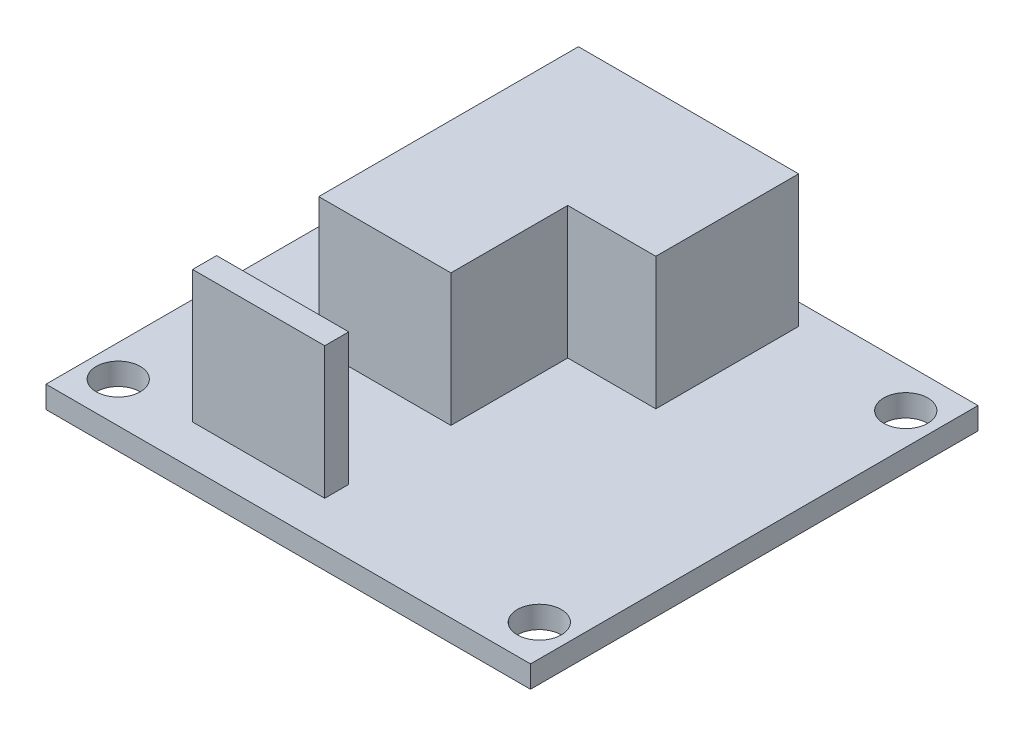
SolidWorks part; units mm, degrees
ref_plane "Front" through (0, 0, 0) normal (0, 0, 1) x (1, 0, 0)
ref_plane "Top" through (0, 0, 0) normal (0, 1, 0) x (1, 0, 0)
ref_plane "Right" through (0, 0, 0) normal (1, 0, 0) x (0, 0, -1)
sketch "Sketch2" plane through (0, 0, 0) normal (0, 1, 0) x (1, 0, 0)
  line L0 (0, -55) -> (0, 55) construction
  line L1 (-17.4625, 16.129) -> (17.4625, 16.129)
  line L2 (-17.4625, 16.129) -> (-17.4625, -16.129)
  line L3 (-17.4625, -16.129) -> (17.4625, -16.129)
  line L4 (17.4625, 16.129) -> (17.4625, -16.129)
  line L5 (-17.4625, 16.129) -> (17.4625, -16.129) construction
  line L6 (-17.4625, -16.129) -> (17.4625, 16.129) construction
  line L7 (-55, 0) -> (55, 0) construction
  line L9 (-9.8168, 14.6038) -> (-0.2918, 14.6038)
  line L10 (-9.8168, 14.6038) -> (-9.8168, -4.1127)
  line L11 (-9.8168, -4.1127) -> (-0.2918, -4.1127)
  line L12 (-0.2918, 14.6038) -> (-0.2918, -4.1127)
  line L13 (-0.2918, 14.6038) -> (6.0582, 14.6038)
  line L14 (-0.2918, 14.6038) -> (-0.2918, 4.3097)
  line L15 (-0.2918, 4.3097) -> (6.0582, 4.3097)
  line L16 (6.0582, 14.6038) -> (6.0582, 4.3097)
  line L17 (-9.8168, -11.4774) -> (-0.2918, -11.4774)
  line L18 (-9.8168, -11.4774) -> (-9.8168, -13.208)
  line L19 (-9.8168, -13.208) -> (-0.2918, -13.208)
  line L20 (-0.2918, -11.4774) -> (-0.2918, -13.208)
  circle A0 centre (-15.1765, 13.208) radius 1.5875
  circle A1 centre (15.1765, 13.208) radius 1.5875
  circle A2 centre (15.1765, -13.208) radius 1.5875
  circle A3 centre (-15.1765, -13.208) radius 1.5875
  point P0 (0, 0)
  dimension "D3" = 3.175
  dimension "D1" = 34.925
  dimension "D2" = 32.258
  dimension "D4" = 2.921
  dimension "D5" = 2.286
  dimension "D6" = 15.875
  dimension "D7" = 9.525
  dimension "D8" = 6.35
extrude "Boss-Extrude1" add sketch "Sketch2" along normal blind 1.5875 contours L4 L1 L2 L3 A1 A0 L13 L16 L15 L12 L11 L10 L9 L17 L20 L19 L18 A2 A3 region at (0.9534, 0, 1.617)
sketch "Sketch3" plane through (0, 1.5875, 0) normal (0, 1, 0) x (1, 0, 0)
  line L0 (-9.8168, 14.6038) -> (6.0582, 14.6038) construction
  line L1 (-9.8168, 14.6038) -> (-9.8168, -4.1127) construction
  line L2 (-9.8168, -4.1127) -> (-0.2918, -4.1127) construction
  line L3 (-0.2918, 4.3097) -> (-0.2918, -4.1127) construction
  line L4 (17.4625, -16.129) -> (17.4625, 16.129)
  line L5 (17.4625, 16.129) -> (-17.4625, 16.129)
  line L6 (-17.4625, 16.129) -> (-17.4625, -16.129)
  line L7 (-17.4625, -16.129) -> (17.4625, -16.129)
  line L8 (17.4625, -16.129) -> (17.4625, 16.129)
  line L9 (17.4625, 16.129) -> (-17.4625, 16.129)
  line L10 (-17.4625, 16.129) -> (-17.4625, -16.129)
  line L11 (-17.4625, -16.129) -> (17.4625, -16.129)
  line L12 (-0.2918, 4.3097) -> (6.0582, 4.3097) construction
  line L13 (6.0582, 14.6038) -> (6.0582, 4.3097) construction
  line L14 (-0.2918, -11.4774) -> (-0.2918, -13.208) construction
  line L15 (-9.8168, -11.4774) -> (-0.2918, -11.4774) construction
  line L16 (-9.8168, -11.4774) -> (-9.8168, -13.208) construction
  line L17 (-9.8168, -13.208) -> (-0.2918, -13.208) construction
  line L18 (-9.8168, -13.208) -> (-0.2918, -13.208)
  line L19 (-9.8168, -11.4774) -> (-9.8168, -13.208)
  line L20 (-9.8168, -11.4774) -> (-0.2918, -11.4774)
  line L21 (-0.2918, -11.4774) -> (-0.2918, -13.208)
  line L22 (6.0582, 14.6038) -> (6.0582, 4.3097)
  line L23 (-0.2918, 4.3097) -> (6.0582, 4.3097)
  line L24 (-0.2918, 4.3097) -> (-0.2918, -4.1127)
  line L25 (-9.8168, -4.1127) -> (-0.2918, -4.1127)
  line L26 (-9.8168, 14.6038) -> (-9.8168, -4.1127)
  line L27 (-9.8168, 14.6038) -> (6.0582, 14.6038)
  line M21 (-9.8168, 14.6038) -> (6.0582, 14.6038)
  line M22 (6.0582, 14.6038) -> (6.0582, 4.3097)
  line M23 (6.0582, 4.3097) -> (-0.2918, 4.3097)
  line M24 (-0.2918, 4.3097) -> (-0.2918, -4.1127)
  line M25 (-0.2918, -4.1127) -> (-9.8168, -4.1127)
  line M26 (-9.8168, -4.1127) -> (-9.8168, 14.6038)
  line M27 (-9.8168, -11.4774) -> (-0.2918, -11.4774)
  line M28 (-0.2918, -11.4774) -> (-0.2918, -13.208)
  line M29 (-0.2918, -13.208) -> (-9.8168, -13.208)
  line M30 (-9.8168, -13.208) -> (-9.8168, -11.4774)
  dimension "D1" = 0
extrude "Boss-Extrude2" add sketch "Sketch3" along normal blind 9.525 separate body contours M21 M26 M25 M24 M23 M22 | M27 M30 M29 M28 region at (-5.0543, 1.5875, 12.3427) region at (-2.9247, 1.5875, -6.3754)
